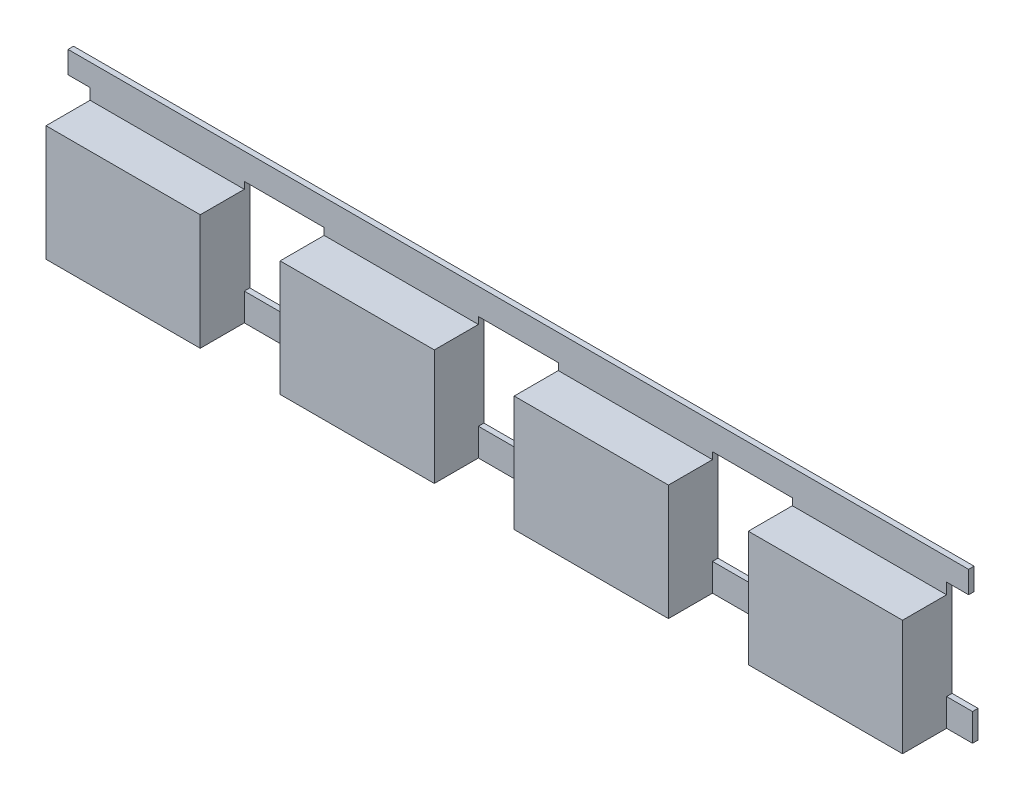
SolidWorks part; units mm, degrees
ref_plane "Спереди" through (0, 0, 0) normal (0, 0, 1) x (1, 0, 0)
ref_plane "Сверху" through (0, 0, 0) normal (0, 1, 0) x (1, 0, 0)
ref_plane "Справа" through (0, 0, 0) normal (1, 0, 0) x (0, 0, -1)
other "Configuration Table"
sketch "Эскиз1" plane through (0, 0, 0) normal (0, 0, 1) x (1, 0, 0)
  line L1 (-2.8, -2.1) -> (2.8, -2.1)
  line L2 (-2.8, -2.1) -> (-2.8, 2.1)
  line L3 (-2.8, 2.1) -> (2.8, 2.1)
  line L4 (2.8, -2.1) -> (2.8, 2.1)
  line L5 (-2.8, -2.1) -> (2.8, 2.1) construction
  line L6 (-2.8, 2.1) -> (2.8, -2.1) construction
  point P0 (0, 0)
  dimension "D1" = 4.2
  dimension "D2" = 5.6
extrude "Бобышка-Вытянуть1" add sketch "Эскиз1" along normal blind 1.4
sketch "Эскиз2" plane through (0, 0, 1.4) normal (0, 0, 1) x (1, 0, 0)
  line L0 (0, 0) -> (-1.0279, 0)
sketch "Эскиз3" plane through (0, 0, 0) normal (0, 0, -1) x (-1, 0, 0)
  line L1 (2.8, 2.1) -> (-28.3, 2.1)
  line L2 (2.8, 2.1) -> (2.8, 3.3)
  line L3 (2.8, 3.3) -> (-28.3, 3.3)
  line L4 (-28.3, 2.1) -> (-28.3, 3.3)
  line L5 (2.8, 2.1) -> (-28.3, 2.1)
  line L6 (2.8, 2.1) -> (2.8, 1.8)
  line L7 (2.8, 1.8) -> (-28.3, 1.8)
  line L8 (-28.3, 2.1) -> (-28.3, 1.8)
  line M5 (-2.8, 2.1) -> (-2.8, -2.1)
  line M7 (2.8, -2.1) -> (2.8, 2.1)
  line M8 (2.8, 2.1) -> (-2.8, 2.1)
  dimension "D1" = 1.2
  dimension "D2" = 0.3
  dimension "D3" = 31.1
  dimension "D4" = 31.1
extrude "Бобышка-Вытянуть2" add sketch "Эскиз3" against normal blind 0.2 contours L4 L1 L2 L3 M8 | L1 L8 L7 M5 | L7 M7 M8 M5 region at (0, 1.95, 0) region at (12.75, 2.7, 0) region at (15.55, 1.95, 0)
pattern_linear "Линейный массив1" count 4 spacing 8.5 along (1, 0, 0) of "Бобышка-Вытянуть1"
sketch "Эскиз4" plane through (0, 0, 0) normal (0, 0, -1) x (-1, 0, 0)
  line L0 (-22.7, 1.8) -> (-19.8, 1.8)
  line L2 (-22.7, 2.35) -> (-19.8, 2.35)
  line L3 (-22.7, 2.35) -> (-22.7, 1.25)
  line L4 (-22.7, 1.25) -> (-19.8, 1.25)
  line L5 (-19.8, 2.35) -> (-19.8, 1.25)
  line L6 (-22.7, 2.35) -> (-19.8, 1.25) construction
  line L7 (-22.7, 1.25) -> (-19.8, 2.35) construction
  line L8 (-14.2, 2.35) -> (-14.2, 1.25)
  line L9 (-14.2, 2.35) -> (-11.3, 2.35)
  line L10 (-11.3, 2.35) -> (-11.3, 1.25)
  line L11 (-14.2, 1.25) -> (-11.3, 1.25)
  line L12 (-5.7, 2.35) -> (-5.7, 1.25)
  line L13 (-5.7, 2.35) -> (-2.8, 2.35)
  line L14 (-2.8, 2.35) -> (-2.8, 1.25)
  line L15 (-5.7, 1.25) -> (-2.8, 1.25)
  point P4 (-21.25, 1.8)
  dimension "D1" = 1.1
  dimension "D2" = 3
extrude "Вырез-Вытянуть1" cut sketch "Эскиз4" against normal blind 0.2 contours L12 L15 L14 L13 | L8 L11 L10 L9 | L5 L0 L4 | L5 L2 L3 L0 region at (21.25, 2.075, 0) region at (21.25, 1.525, 0) region at (12.75, 1.8, 0) region at (4.25, 1.8, 0)
sketch "Эскиз5" plane through (28.3, 0, 0) normal (1, 0, 0) x (0, 0, -1)
  line L0 (0, -2.1) -> (0, 3.3) construction
  line L1 (-0.2, 3.3) -> (0, 3.3)
  line L2 (-0.2, 3.3) -> (-0.2, 2.5)
  line L3 (-0.2, 2.5) -> (0, 2.5)
  line L4 (0, 3.3) -> (0, 2.5)
  dimension "D1" = 0.8
extrude "Бобышка-Вытянуть3" add sketch "Эскиз5" along normal blind 0.8
sketch "Эскиз6" plane through (-2.8, 0, 0) normal (-1, 0, 0) x (0, 0, 1)
  line L0 (0.2, 2.1) -> (0.2, 3.3) construction
  line L1 (0, 3.3) -> (0.2, 3.3)
  line L2 (0, 3.3) -> (0, 2.5)
  line L3 (0, 2.5) -> (0.2, 2.5)
  line L4 (0.2, 3.3) -> (0.2, 2.5)
  dimension "D1" = 0.8
extrude "Бобышка-Вытянуть4" add sketch "Эскиз6" along normal blind 0.8
sketch "Эскиз7" plane through (0, 0, 0) normal (0, 0, -1) x (-1, 0, 0)
  line L1 (-29.2405, -2.1) -> (3.6437, -2.1)
  line L2 (-29.2405, -2.1) -> (-29.2405, -1.1)
  line L3 (-29.2405, -1.1) -> (3.6437, -1.1)
  line L4 (3.6437, -2.1) -> (3.6437, -1.1)
  dimension "D1" = 1
extrude "Бобышка-Вытянуть5" add sketch "Эскиз7" against normal blind 0.2
sketch "Эскиз8" plane through (0, 0, 1.4) normal (0, 0, 1) x (1, 0, 0)
  line L0 (28.3, -2.1) -> (28.3, 2.1) construction
  line L1 (28.3, 2.1) -> (22.7, 2.1) construction
  line L2 (22.7, 2.1) -> (22.7, -2.1) construction
  line L3 (22.7, -2.1) -> (28.3, -2.1) construction
  line L4 (19.8, -2.1) -> (19.8, 2.1) construction
  line L5 (19.8, 2.1) -> (14.2, 2.1) construction
  line L6 (14.2, 2.1) -> (14.2, -2.1) construction
  line L7 (14.2, -2.1) -> (19.8, -2.1) construction
  line L8 (11.3, -2.1) -> (11.3, 2.1) construction
  line L9 (11.3, 2.1) -> (5.7, 2.1) construction
  line L10 (5.7, 2.1) -> (5.7, -2.1) construction
  line L11 (5.7, -2.1) -> (11.3, -2.1) construction
  line L12 (2.8, -2.1) -> (2.8, 2.1) construction
  line L13 (2.8, 2.1) -> (-2.8, 2.1) construction
  line L14 (-2.8, 2.1) -> (-2.8, -2.1) construction
  line L15 (-2.8, -2.1) -> (2.8, -2.1) construction
  line L16 (28.3, -2.1) -> (28.3, 2.1)
  line L17 (28.3, 2.1) -> (22.7, 2.1)
  line L18 (22.7, 2.1) -> (22.7, -2.1)
  line L19 (22.7, -2.1) -> (28.3, -2.1)
  line L20 (19.8, -2.1) -> (19.8, 2.1)
  line L21 (19.8, 2.1) -> (14.2, 2.1)
  line L22 (14.2, 2.1) -> (14.2, -2.1)
  line L23 (14.2, -2.1) -> (19.8, -2.1)
  line L24 (11.3, -2.1) -> (11.3, 2.1)
  line L25 (11.3, 2.1) -> (5.7, 2.1)
  line L26 (5.7, 2.1) -> (5.7, -2.1)
  line L27 (5.7, -2.1) -> (11.3, -2.1)
  line L28 (2.8, -2.1) -> (2.8, 2.1)
  line L29 (2.8, 2.1) -> (-2.8, 2.1)
  line L30 (-2.8, 2.1) -> (-2.8, -2.1)
  line L31 (-2.8, -2.1) -> (2.8, -2.1)
  line L32 (11.9, -2.7) -> (11.9, 2.7)
  line L33 (11.9, 2.7) -> (5.1, 2.7)
  line L34 (5.1, 2.7) -> (5.1, -2.7)
  line L35 (5.1, -2.7) -> (11.9, -2.7)
  line L36 (20.4, -2.7) -> (20.4, 2.7)
  line L37 (20.4, 2.7) -> (13.6, 2.7)
  line L38 (13.6, 2.7) -> (13.6, -2.7)
  line L39 (13.6, -2.7) -> (20.4, -2.7)
  line L40 (28.9, -2.7) -> (28.9, 2.7)
  line L41 (28.9, 2.7) -> (22.1, 2.7)
  line L42 (22.1, 2.7) -> (22.1, -2.7)
  line L43 (22.1, -2.7) -> (28.9, -2.7)
  line L44 (3.4, -2.7) -> (3.4, 2.7)
  line L45 (3.4, 2.7) -> (-3.4, 2.7)
  line L46 (-3.4, 2.7) -> (-3.4, -2.7)
  line L47 (-3.4, -2.7) -> (3.4, -2.7)
  line L48 (2.2, -1.5) -> (2.2, 1.5)
  line L49 (2.2, 1.5) -> (-2.2, 1.5)
  line L50 (-2.2, 1.5) -> (-2.2, -1.5)
  line L51 (-2.2, -1.5) -> (2.2, -1.5)
  line L52 (10.7, -1.5) -> (10.7, 1.5)
  line L53 (10.7, 1.5) -> (6.3, 1.5)
  line L54 (6.3, 1.5) -> (6.3, -1.5)
  line L55 (6.3, -1.5) -> (10.7, -1.5)
  line L56 (19.2, -1.5) -> (19.2, 1.5)
  line L57 (19.2, 1.5) -> (14.8, 1.5)
  line L58 (14.8, 1.5) -> (14.8, -1.5)
  line L59 (14.8, -1.5) -> (19.2, -1.5)
  line L60 (27.7, -1.5) -> (27.7, 1.5)
  line L61 (27.7, 1.5) -> (23.3, 1.5)
  line L62 (23.3, 1.5) -> (23.3, -1.5)
  line L63 (23.3, -1.5) -> (27.7, -1.5)
  dimension "D1" = 0.6
  dimension "D2" = 0.6
extrude "Вырез-Вытянуть2" cut sketch "Эскиз8" against normal blind 1 from offset 0.6 contours L50 L51 L48 L49 | L54 L55 L52 L53 | L58 L59 L56 L57 | L62 L63 L60 L61 region at (0, 0, 1.4) region at (8.5, 0, 1.4) region at (17, 0, 1.4) region at (25.5, 0, 1.4) offset against normal yes
sketch "Эскиз9" plane through (0, 0, 1.4) normal (0, 0, 1) x (1, 0, 0)
  line L4 (2.8, -2.1) -> (2.8, 2.1)
  line L5 (2.8, 2.1) -> (-2.8, 2.1)
  line L6 (-2.8, 2.1) -> (-2.8, -2.1)
  line L7 (-2.8, -2.1) -> (2.8, -2.1)
  line L8 (2.8, -2.1) -> (2.8, 2.1)
  line L9 (2.8, 2.1) -> (-2.8, 2.1)
  line L10 (-2.8, 2.1) -> (-2.8, -2.1)
  line L11 (-2.8, -2.1) -> (2.8, -2.1)
  line L12 (11.3, -2.1) -> (11.3, 2.1)
  line L13 (11.3, 2.1) -> (5.7, 2.1)
  line L14 (5.7, 2.1) -> (5.7, -2.1)
  line L15 (5.7, -2.1) -> (11.3, -2.1)
  line L16 (11.3, -2.1) -> (11.3, 2.1)
  line L17 (11.3, 2.1) -> (5.7, 2.1)
  line L18 (5.7, 2.1) -> (5.7, -2.1)
  line L19 (5.7, -2.1) -> (11.3, -2.1)
  line L20 (19.8, -2.1) -> (19.8, 2.1)
  line L21 (19.8, 2.1) -> (14.2, 2.1)
  line L22 (14.2, 2.1) -> (14.2, -2.1)
  line L23 (14.2, -2.1) -> (19.8, -2.1)
  line L24 (19.8, -2.1) -> (19.8, 2.1)
  line L25 (19.8, 2.1) -> (14.2, 2.1)
  line L26 (14.2, 2.1) -> (14.2, -2.1)
  line L27 (14.2, -2.1) -> (19.8, -2.1)
  line L28 (28.3, -2.1) -> (28.3, 2.1)
  line L29 (28.3, 2.1) -> (22.7, 2.1)
  line L30 (22.7, 2.1) -> (22.7, -2.1)
  line L31 (22.7, -2.1) -> (28.3, -2.1)
  line L32 (28.3, -2.1) -> (28.3, 2.1)
  line L33 (28.3, 2.1) -> (22.7, 2.1)
  line L34 (22.7, 2.1) -> (22.7, -2.1)
  line L35 (22.7, -2.1) -> (28.3, -2.1)
  dimension "D1" = 0
  dimension "D2" = 0
  dimension "D3" = 0
  dimension "D4" = 0
extrude "Бобышка-Вытянуть6" add sketch "Эскиз9" along normal blind 0.4
